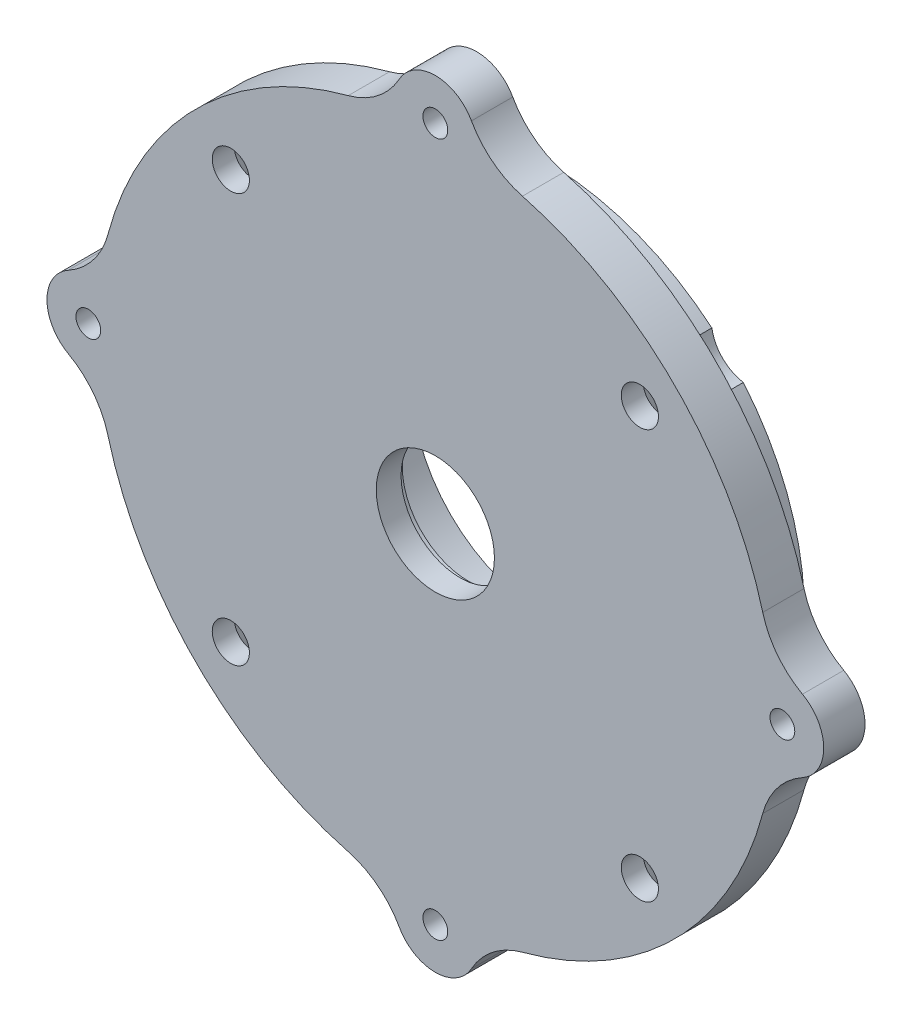
SolidWorks part; units mm, degrees
ref_plane "Ön Düzlem" through (0, 0, 0) normal (0, 0, 1) x (1, 0, 0)
ref_plane "Üst Düzlem" through (0, 0, 0) normal (0, 1, 0) x (1, 0, 0)
ref_plane "Sağ Düzlem" through (0, 0, 0) normal (1, 0, 0) x (0, 0, -1)
sketch "Çizim1" plane through (0, 0, 0) normal (0, 0, 1) x (1, 0, 0)
  circle A0 centre (0, 0) radius 16.1
  circle A1 centre (0, 0) radius 22.5
  circle A2 centre (0, 0) radius 31.4
  circle A3 centre (0, 0) radius 29.425
  dimension "D1" = 32.2
  dimension "D2" = 45
  dimension "D3" = 62.8
  dimension "D4" = 58.85
extrude "Yükseklik-Ekstrüzyon1" add sketch "Çizim1" along normal blind 8.25 contours A1 A0 | A2 A3 region at (-21.8636, 0, 0) region at (-30.5119, 0, 0)
sketch "Çizim2" plane through (0, 0, 8.25) normal (0, 0, 1) x (1, 0, 0)
  circle A0 centre (-24.75, 24.75) radius 2
  circle A1 centre (24.75, 24.75) radius 2
  circle A2 centre (24.75, -24.75) radius 2
  circle A3 centre (-24.75, -24.75) radius 2
  arc A6 (-10.5408, 39.6218) -> (-39.6218, 10.5408) centre (0, 0) ccw
  circle A7 centre (0, 42) radius 1.5
  arc A8 (4.3706, 44.4286) -> (-4.3706, 44.4286) centre (0, 42) ccw
  arc A9 (-4.3706, 44.4286) -> (-10.5408, 39.6218) centre (-13.1118, 49.2857) cw
  arc A10 (4.3706, 44.4286) -> (10.5408, 39.6218) centre (13.1118, 49.2857) ccw
  arc A11 (44.4286, 4.3706) -> (39.6218, 10.5408) centre (49.2857, 13.1118) cw
  arc A12 (44.4286, -4.3706) -> (44.4286, 4.3706) centre (42, 0) ccw
  circle A13 centre (42, 0) radius 1.5
  arc A14 (44.4286, -4.3706) -> (39.6218, -10.5408) centre (49.2857, -13.1118) ccw
  arc A15 (4.3706, -44.4286) -> (10.5408, -39.6218) centre (13.1118, -49.2857) cw
  arc A16 (-4.3706, -44.4286) -> (4.3706, -44.4286) centre (0, -42) ccw
  circle A17 centre (0, -42) radius 1.5
  arc A18 (-4.3706, -44.4286) -> (-10.5408, -39.6218) centre (-13.1118, -49.2857) ccw
  arc A19 (-44.4286, -4.3706) -> (-39.6218, -10.5408) centre (-49.2857, -13.1118) cw
  arc A20 (-44.4286, 4.3706) -> (-44.4286, -4.3706) centre (-42, 0) ccw
  circle A21 centre (-42, 0) radius 1.5
  arc A22 (-44.4286, 4.3706) -> (-39.6218, 10.5408) centre (-49.2857, 13.1118) ccw
  arc A23 (-39.6218, -10.5408) -> (-10.5408, -39.6218) centre (0, 0) ccw
  arc A24 (10.5408, -39.6218) -> (39.6218, -10.5408) centre (0, 0) ccw
  arc A25 (39.6218, 10.5408) -> (10.5408, 39.6218) centre (0, 0) ccw
  circle A26 centre (0, 0) radius 7.15
  point P0 (0, 0)
  point P17 (0, 0)
  point P48 (0, 0)
  dimension "D3" = 4
  dimension "D4" = 24.75
  dimension "D5" = 24.75
  dimension "D1" = 82
  dimension "D2" = 42
  dimension "D7" = 10
  dimension "D8" = 3
  dimension "D9" = 10
  dimension "D10" = 10
  dimension "D12" = 14.3
  dimension "D6" = 4
  dimension "D11" = 4
extrude "Yükseklik-Ekstrüzyon2" add sketch "Çizim2" along normal blind 5
hole_wizard "M4 Altıgen Alyan Havşa Başlı Vida İçin Havşa2" positions "3B Çizim1" profile "Çizim5" countersink size "M4" standard "DIN" end condition through all
sketch3d "3B Çizim1"
  line L0 (24.75, 24.75, 13.25) -> (24.75, 24.75, 8.25) construction
  line L1 (-24.75, 24.75, 13.25) -> (-24.75, 24.75, 8.25) construction
  line L2 (-24.75, -24.75, 13.25) -> (-24.75, -24.75, 8.25) construction
  line L3 (24.75, -24.75, 13.25) -> (24.75, -24.75, 8.25) construction
  point P0 (24.75, 24.75, 8.25)
  point P4 (-24.75, 24.75, 8.25)
  point P8 (-24.75, -24.75, 8.25)
  point P12 (24.75, -24.75, 8.25)
sketch "Çizim5" plane through (24.75, 24.75, 8.25) normal (1, 0, 0) x (0, 1, 0)
  line L0 (0, 0) -> (0, 5)
  line L1 (0, 5) -> (2.25, 5)
  line L2 (2.25, 5) -> (2.25, 2.34)
  line L3 (2.25, 2.34) -> (4.59, 0)
  line L5 (4.59, 0) -> (0, 0)
  line L6 (-2.25, 2.34) -> (-4.59, 0) construction
  line L11 (0, -6.35) -> (0, 107.95) construction
  dimension "Thru Hole Dia." = 4.5
  dimension "Thru Hole Depth" = 5
  dimension "Near C'Sink Dia." = 9.18
  dimension "Near C'Sink Angle" = 90
sketch "Çizim6" plane through (0, 0, 0) normal (0, 0, -1) x (-1, 0, 0)
  circle A0 centre (-24.75, 24.75) radius 4.59
  circle A1 centre (24.75, 24.75) radius 4.59
  circle A2 centre (24.75, -24.75) radius 4.59
  circle A3 centre (-24.75, -24.75) radius 4.59
  point P3 (79.2176, -20.6954)
  point P4 (0, 0)
  point P12 (0, 0)
  dimension "D1" = 9.18
  dimension "D2" = 4
extrude "Kes-Ekstrüzyon1" cut sketch "Çizim6" against normal up to surface (8.25 mm away) up to face at (0, 0, 8.25)
sketch "Çizim7" plane through (0, 0, 8.25) normal (0, 0, -1) x (-1, 0, 0)
  circle A0 centre (0, 0) radius 16.1 construction
  circle A1 centre (0, 0) radius 16.1
extrude "Kes-Ekstrüzyon2" cut sketch "Çizim7" against normal blind 1
sketch "Çizim8" plane through (0, 0, 9.25) normal (0, 0, -1) x (-1, 0, 0)
  circle A0 centre (0, 0) radius 8
  dimension "D1" = 16
extrude "Kes-Ekstrüzyon3" cut sketch "Çizim8" against normal blind 1
